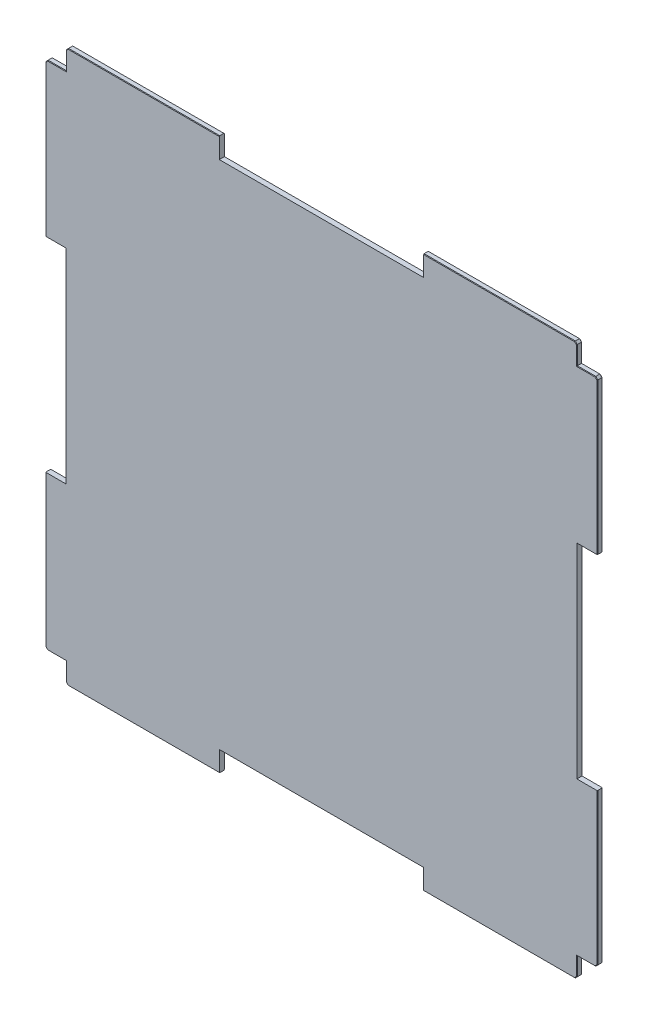
SolidWorks part; units mm, degrees
material "PET"
ref_plane "Front Plane" through (0, 0, 0) normal (0, 0, 1) x (1, 0, 0)
ref_plane "Top Plane" through (0, 0, 0) normal (0, 1, 0) x (1, 0, 0)
ref_plane "Right Plane" through (0, 0, 0) normal (1, 0, 0) x (0, 0, -1)
sketch "Sketch1" plane through (0, 0, 0) normal (0, 0, 1) x (1, 0, 0)
  line L1 (0, 0) -> (540, 0)
  line L2 (0, 0) -> (0, 540)
  line L3 (0, 540) -> (540, 540)
  line L4 (540, 0) -> (540, 540)
  dimension "D1" = 540
  dimension "D2" = 540
extrude "Boss-Extrude1" add sketch "Sketch1" along normal blind 5
sketch "Sketch2" plane through (0, 0, 5) normal (0, 0, 1) x (1, 0, 0)
  line L1 (0, 540) -> (20, 540)
  line L2 (0, 540) -> (0, 520)
  line L3 (0, 520) -> (20, 520)
  line L4 (20, 540) -> (20, 520)
  line L5 (540, 540) -> (520, 540)
  line L6 (540, 540) -> (540, 520)
  line L7 (540, 520) -> (520, 520)
  line L8 (520, 540) -> (520, 520)
  line L9 (540, 0) -> (520, 0)
  line L10 (540, 0) -> (540, 20)
  line L11 (540, 20) -> (520, 20)
  line L12 (520, 0) -> (520, 20)
  line L13 (0, 0) -> (20, 0)
  line L14 (0, 0) -> (0, 20)
  line L15 (0, 20) -> (20, 20)
  line L16 (20, 0) -> (20, 20)
  dimension "D1" = 20
  dimension "D2" = 20
  dimension "D3" = 20
  dimension "D4" = 20
  dimension "D5" = 20
  dimension "D6" = 20
  dimension "D7" = 20
  dimension "D8" = 20
extrude "Cut-Extrude1" cut sketch "Sketch2" against normal blind 5
chamfer "Chamfer1" distance 2 angle 45 8 edges at (0, 520, 2.5) (20, 540, 2.5) (520, 540, 2.5) (540, 520, 2.5) (20, 0, 2.5) (0, 20, 2.5) (540, 20, 2.5) (520, 0, 2.5)
chamfer "Chamfer2" distance 0.5 angle 45 40 edges at (1, 21, 0) (11, 20, 0) (20, 11, 0) (21, 1, 0) (270, 0, 0) (519, 1, 0) (520, 11, 0) (529, 20, 0) (539, 21, 0) (540, 270, 0) (539, 519, 0) (529, 520, 0) (520, 529, 0) (519, 539, 0) (270, 540, 0) (21, 539, 0) (20, 529, 0) (11, 520, 0) (1, 519, 0) (0, 270, 0) (20, 529, 5) (21, 539, 5) (270, 540, 5) (519, 539, 5) (520, 529, 5) (529, 520, 5) (539, 519, 5) (540, 270, 5) (539, 21, 5) (529, 20, 5) (520, 11, 5) (519, 1, 5) (270, 0, 5) (21, 1, 5) (20, 11, 5) (11, 20, 5) (1, 21, 5) (0, 270, 5) (1, 519, 5) (11, 520, 5)
sketch "Sketch3" plane through (0, 0, 5) normal (0, 0, 1) x (1, 0, 0)
  line L5 (270, 0.5) -> (270, 539.5) construction
  line L6 (22.2071, 0.5) -> (517.7929, 0.5) construction
  line L7 (22, 540) -> (518, 540) construction
  line L8 (170, 597.4166) -> (370, 597.4166)
  line L9 (170, 597.4166) -> (170, 520)
  line L10 (170, 520) -> (370, 520)
  line L11 (370, 597.4166) -> (370, 520)
  dimension "D1" = 200
  dimension "D2" = 100
  dimension "D3" = 20
extrude "Cut-Extrude2" cut sketch "Sketch3" against normal blind 10
sketch "Sketch4" plane through (0, 0, 5) normal (0, 0, 1) x (1, 0, 0)
  line L0 (519.5, 519.5) -> (20.5, 20.5) construction
  circle A0 centre (270, 270) radius 63.302
ref_axis "Axis1" through (270, 270, 5) along (0, 0, 1)
pattern_circular "CirPattern1" count 4 over 360 about axis through (270, 270, 5) along (0, 0, 1) of "Cut-Extrude2"
